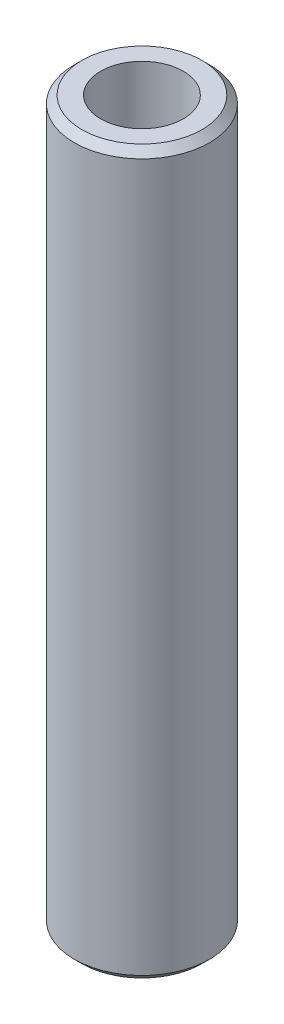
SolidWorks part; units mm, degrees
ref_plane "Front Plane" through (0, 0, 0) normal (0, 0, 1) x (1, 0, 0)
ref_plane "Top Plane" through (0, 0, 0) normal (0, 1, 0) x (1, 0, 0)
ref_plane "Right Plane" through (0, 0, 0) normal (1, 0, 0) x (0, 0, -1)
sketch "Sketch1" plane through (0, 0, 0) normal (0, 1, 0) x (1, 0, 0)
  circle A0 centre (0, 0) radius 10
  dimension "SHAFT_OD" = 20
extrude "Boss-Extrude1" add sketch "Sketch1" along normal blind 106.8543
sketch "Sketch2" plane through (0, 0, 0) normal (0, 1, 0) x (1, 0, 0)
  circle A0 centre (0, 0) radius 6.114
  dimension "BORE_D" = 12.2279
extrude "Cut-Extrude1" cut sketch "Sketch2" along normal through all
chamfer "Chamfer1" distance 1.1171 angle 45 2 edges at (0, 106.8543, 10) (0, 0, 10)
